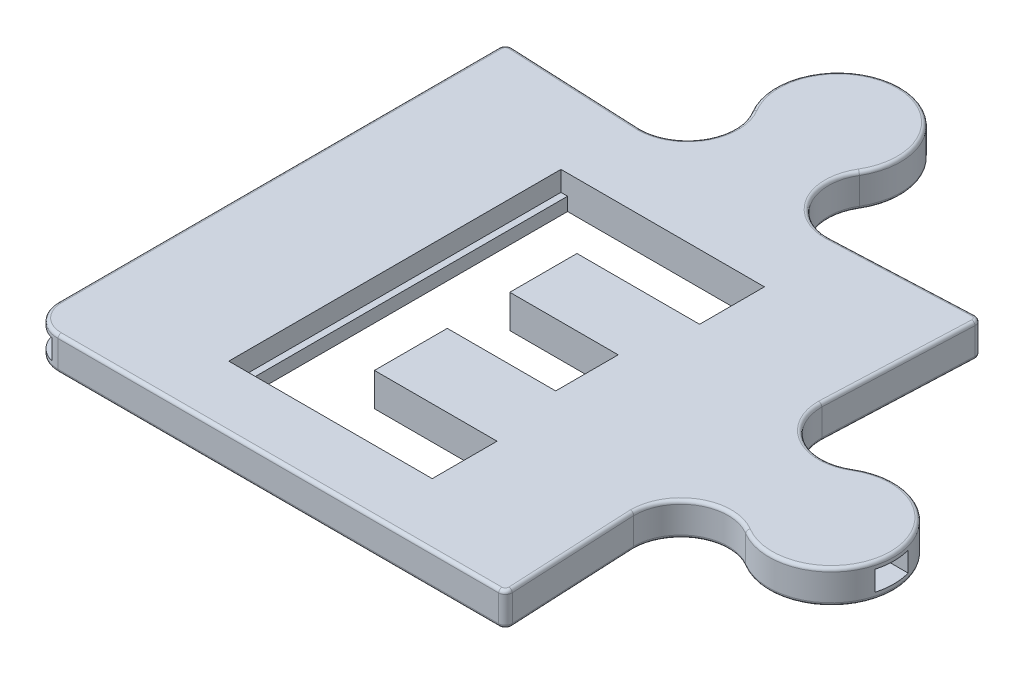
SolidWorks part; units mm, degrees
ref_plane "Front Plane" through (0, 0, 0) normal (0, 0, 1) x (1, 0, 0)
ref_plane "Top Plane" through (0, 0, 0) normal (0, 1, 0) x (1, 0, 0)
ref_plane "Right Plane" through (0, 0, 0) normal (1, 0, 0) x (0, 0, -1)
sketch "Sketch1" plane through (0, 0, 0) normal (0, 1, 0) x (1, 0, 0)
  line L0 (-31, -36) -> (37, -36) construction
  line L1 (-36, 37) -> (-36, -31) construction
  line L2 (-14.1421, 36) -> (-36, 37) construction
  line L3 (37, 37) -> (14.1421, 36) construction
  line L4 (36, 13.1421) -> (37, 37) construction
  line L5 (37, -36) -> (36, -15.1421) construction
  line L6 (-35.4, 36.3719) -> (-35.4, -31)
  line L7 (-36, 36) -> (36, 36) construction
  line L8 (-36, 36) -> (-36, -36) construction
  line L9 (-36, -36) -> (36, -36) construction
  line L10 (36, 36) -> (36, -36) construction
  line L11 (-31, -35.4) -> (36.3705, -35.4)
  line L12 (36.3705, -35.4) -> (35.4, -15.1568)
  line L13 (35.4, 13.155) -> (36.3732, 36.372)
  line L14 (36.3732, 36.372) -> (14.1555, 35.4)
  line L15 (-14.1562, 35.4) -> (-35.4, 36.3719)
  line L16 (-30, -24) -> (30, -24) construction
  line L17 (-30, 29) -> (30, 29) construction
  line L18 (-30, 29) -> (-30, -31) construction
  line L19 (-30, -31) -> (30, -31) construction
  line L20 (30, 29) -> (30, -31) construction
  line L21 (-30, 24) -> (30, 24) construction
  line L22 (-30, 24) -> (-30, -26) construction
  line L23 (-30, -26) -> (30, -26) construction
  line L24 (30, 24) -> (30, -26) construction
  arc A0 (-36, -31) -> (-31, -36) centre (-31, -31) ccw construction
  arc A1 (-14.1421, 36) -> (-8.571, 45.8485) centre (-14.1421, 42.5) ccw construction
  arc A2 (8.571, 45.8485) -> (-8.571, 45.8485) centre (0, 51) ccw construction
  arc A3 (8.571, 45.8485) -> (14.1421, 36) centre (14.1421, 42.5) ccw construction
  arc A4 (36, 13.1421) -> (45.8485, 7.571) centre (42.5, 13.1421) ccw construction
  arc A5 (45.8485, -9.571) -> (45.8485, 7.571) centre (51, -1) ccw construction
  arc A6 (45.8485, -9.571) -> (36, -15.1421) centre (42.5, -15.1421) ccw construction
  arc A7 (-35.4, -31) -> (-31, -35.4) centre (-31, -31) ccw
  arc A8 (46.1576, -9.0567) -> (35.4, -15.1568) centre (42.5, -15.1421) ccw
  arc A9 (46.1576, -9.0567) -> (46.1576, 7.0567) centre (51, -1) ccw
  arc A10 (35.4, 13.155) -> (46.1576, 7.0567) centre (42.5, 13.1421) ccw
  arc A11 (8.0567, 46.1576) -> (14.1555, 35.4) centre (14.1421, 42.5) ccw
  arc A12 (8.0567, 46.1576) -> (-8.0567, 46.1576) centre (0, 51) ccw
  arc A13 (-14.1562, 35.4) -> (-8.0567, 46.1576) centre (-14.1421, 42.5) ccw
  point P32 (36, 0)
  point P34 (0, 36)
  dimension "D5" = 6.5
  dimension "D6" = 10
  dimension "D7" = 6.5
  dimension "D13" = 5
  dimension "D9" = 10
  dimension "D11" = 6.5
  dimension "D12" = 6.5
  dimension "D1" = 72
  dimension "D2" = 1
  dimension "D3" = 1
  dimension "D4" = 15
  dimension "D8" = 1
  dimension "D10" = 35
  dimension "D14" = 15
  dimension "D15" = 36
  dimension "D16" = 1
  dimension "D18" = 60
  dimension "D19" = 60
  dimension "D20" = 5
  dimension "D21" = 6
  dimension "D22" = 5
  dimension "D23" = 50
  dimension "D24" = 2
  dimension "D17" = 0.6
extrude "Boss-Extrude1" add sketch "Sketch1" along normal blind 5
sketch "Sketch6" plane through (0, 0, 0) normal (0, -1, 0) x (1, 0, 0)
  line L0 (-35.4, -36.3719) -> (-35.4, 31) construction
  line L1 (-35.4, 17.9) -> (-27.4, 17.9)
  line L2 (-35.4, 17.9) -> (-35.4, -16.1)
  line L3 (-35.4, -16.1) -> (-27.4, -16.1)
  line L4 (-27.4, 17.9) -> (-27.4, -16.1)
  line L5 (-31, 35.4) -> (36.3705, 35.4) construction
  line L6 (-35.4, 14.65) -> (-30.4, 14.65)
  line L7 (-35.4, 14.65) -> (-35.4, -12.85)
  line L8 (-35.4, -12.85) -> (-30.4, -12.85)
  line L9 (-30.4, 14.65) -> (-30.4, -12.85)
  point P15 (-27.4, 0.9)
  point P16 (-30.4, 0.9)
  line M28 (-35.4, 31) -> (-35.4, -36.3719)
  dimension "D1" = 8
  dimension "D2" = 20.75
  dimension "D3" = 27.5
  dimension "D4" = 5
  dimension "D5" = 34
extrude "Cut-Extrude3" cut sketch "Sketch6" against normal blind 3 from offset 1 contours L6 L9 L8 L3 L4 L1 M28 | L9 L6 L2 L8 region at (-29.8665, 0, 0.9) region at (-32.9, 0, 0.9) offset against normal yes
extrude "Cut-Extrude4" cut sketch "Sketch6<3>" against normal up to next contours L9 L6 L2 L8 region at (-32.9, 0, 0.9)
sketch "Sketch6<3>" plane through (0, 0, 0) normal (0, -1, 0) x (1, 0, 0) same geometry as "Sketch6"
sketch "Sketch8" plane through (0, 0, 0) normal (0, -1, 0) x (1, 0, 0)
  line L1 (-2.5, -51.4) -> (2.5, -51.4)
  line L2 (-2.5, -51.4) -> (-2.5, -60.4)
  line L3 (-2.5, -60.4) -> (2.5, -60.4)
  line L4 (2.5, -51.4) -> (2.5, -60.4)
  line L5 (51.4, 3.5) -> (60.4, 3.5)
  line L6 (51.4, 3.5) -> (51.4, -1.5)
  line L7 (51.4, -1.5) -> (60.4, -1.5)
  line L8 (60.4, 3.5) -> (60.4, -1.5)
  arc A0 (-8.0567, -46.1576) -> (8.0567, -46.1576) centre (0, -51) ccw construction
  arc A1 (46.1576, -7.0567) -> (46.1576, 9.0567) centre (51, 1) ccw construction
  point P4 (0, -60.4)
  point P13 (60.4, 1)
  dimension "D1" = 5
  dimension "D2" = 9
  dimension "D3" = 5
  dimension "D4" = 9
extrude "Cut-Extrude5" cut sketch "Sketch8" against normal blind 3 from offset 1 offset against normal yes
sketch "Sketch9" plane through (0, 0, 0) normal (0, -1, 0) x (1, 0, 0)
  line L0 (-31, 35.4) -> (36.3705, 35.4) construction
  line L1 (-35.4, 14.65) -> (-35.4, 31) construction
  line L2 (-31.7636, 35.3332) -> (-35.4, 31) construction
  line L3 (-33.2571, 29.735) -> (-30.0429, 33.565) construction
  line L4 (-30.0429, 33.565) -> (-33.2571, 29.735) construction
  line L5 (-30.0429, 33.565) -> (-32.7119, 35.8048)
  line L6 (-33.2571, 29.735) -> (-35.926, 31.9747)
  line L7 (-32.7119, 35.8048) -> (-35.926, 31.9747)
  circle A0 centre (-31.65, 31.65) radius 2.5
  arc A1 (-31, 35.4) -> (-35.4, 31) centre (-31, 31) ccw construction
  arc M41 (-31, 35.4) -> (-35.4, 31) centre (-31, 31) ccw
  dimension "D1" = 5
  dimension "D3" = 3.75
  dimension "D4" = 5.6569
  dimension "D2" = 3.75
extrude "Cut-Extrude6" cut sketch "Sketch9" against normal blind 3 from offset 1 contours A0 L5 L6 M41 | A0 L5 region at (-33.6239, 0, 33.3064) region at (-31.65, 0, 31.65) offset against normal yes
sketch "Sketch11" plane through (-35.4, 0, 0) normal (-1, 0, 0) x (0, 0, 1)
  line L0 (-13.155, 0) -> (-36.372, 0) construction
  line L1 (-25.1, 3) -> (-19.1, 3)
  line L2 (-25.1, 3) -> (-25.1, 1.5)
  line L3 (-25.1, 1.5) -> (-19.1, 1.5)
  line L4 (-19.1, 3) -> (-19.1, 1.5)
  line L5 (-16.1, 4) -> (-16.1, 1) construction
  line L6 (35.4, 0) -> (15.1568, 0) construction
  line L7 (20.9, 3) -> (26.9, 3)
  line L8 (20.9, 3) -> (20.9, 1.5)
  line L9 (20.9, 1.5) -> (26.9, 1.5)
  line L10 (26.9, 3) -> (26.9, 1.5)
  line L12 (17.9, 4) -> (17.9, 1) construction
  dimension "D1" = 3
  dimension "D2" = 1.5
  dimension "D3" = 3
  dimension "D4" = 6
  dimension "D5" = 3
  dimension "D6" = 1.5
  dimension "D7" = 6
  dimension "D8" = 3
fillet "Fillet1" radius 0.5 17 edges at (-35.4, 0, 22.825) (-34.1113, 0, 34.1113) (2.6853, 0, 35.4) (35.8853, 0, 25.2784) (38.9978, 0, 8.966) (60.4, 0, 1) (38.9986, 0, -6.9655) (35.8866, 0, -24.7635) (25.2643, 0, -35.886) (7.9657, 0, -38.9984) (0, 0, -60.4) (-7.9658, 0, -38.9981) (-24.7781, 0, -35.886) (-35.4, 0, -24.611) (-32.9, 0, -12.85) (-30.4, 0, 0.9) (-32.9, 0, 14.65)
fillet "Fillet2" radius 0.5 13 edges at (-7.9658, 5, -38.9981) (0, 5, -60.4) (7.9657, 5, -38.9984) (25.2643, 5, -35.886) (35.8866, 5, -24.7635) (38.9986, 5, -6.9655) (60.4, 5, 1) (38.9978, 5, 8.966) (35.8853, 5, 25.2784) (2.6853, 5, 35.4) (-34.1113, 5, 34.1113) (-35.4, 5, -2.686) (-24.7781, 5, -35.886)
fillet "Fillet3" radius 1 9 edges at (36.2202, 0.1464, -36.2187) (36.2202, 4.8536, -36.2187) (36.3732, 2.5, -36.372) (-35.2536, 0.1464, -36.2186) (-35.2536, 4.8536, -36.2186) (36.2169, 0.1464, 35.2536) (36.2169, 4.8536, 35.2536) (36.3705, 2.5, 35.4) (-35.4, 2.5, -36.3719)
extrude "Cut-Extrude9" cut sketch "Sketch11" against normal blind 3
chamfer "Chamfer1" distance 1 angle 50 2 edges at (-35.4, 1.5, 23.9) (-35.4, 1.5, -22.1) first distance on face at (-35.4, 2.25, -22.1)
sketch "Sketch12" plane through (0, 5, 0) normal (0, 1, 0) x (1, 0, 0)
  text T0 "E" font "Poppins" height 50
extrude "Cut-Extrude10" cut sketch "Sketch12" against normal through all
sketch "Sketch13" plane through (0, 0, 0) normal (0, -1, 0) x (1, 0, 0)
  line L0 (-14.7053, 26) -> (-14.7053, -24) construction
  line L1 (-14.7053, 26) -> (-13.7053, 26)
  line L2 (-14.7053, 26) -> (-14.7053, -24)
  line L3 (-14.7053, -24) -> (-13.7053, -24)
  line L4 (-13.7053, 26) -> (-13.7053, -24)
  line L5 (-30, 26) -> (30, 26) construction
  line L6 (-14.7053, -24) -> (15.9213, -24) construction
  line L7 (-2.535, 16.2411) -> (15.9213, 16.2411) construction
  line L8 (15.9213, 26) -> (14.9213, 26)
  line L9 (15.9213, 26) -> (15.9213, 16.2411)
  line L10 (15.9213, 16.2411) -> (14.9213, 16.2411)
  line L11 (14.9213, 26) -> (14.9213, 16.2411)
  line L12 (-2.535, -4.1319) -> (13.7778, -4.1319) construction
  line L13 (13.7778, 5.2766) -> (12.7778, 5.2766)
  line L14 (13.7778, 5.2766) -> (13.7778, -4.1319)
  line L15 (13.7778, -4.1319) -> (12.7778, -4.1319)
  line L16 (12.7778, 5.2766) -> (12.7778, -4.1319)
  line L18 (15.9213, -14.2411) -> (14.9213, -14.2411)
  line L19 (15.9213, -14.2411) -> (15.9213, -24)
  line L20 (15.9213, -24) -> (14.9213, -24)
  line L21 (14.9213, -14.2411) -> (14.9213, -24)
  dimension "D1" = 1
  dimension "D2" = 1
  dimension "D3" = 1
  dimension "D4" = 1
extrude "Boss-Extrude2" add sketch "Sketch13" against normal blind 2
